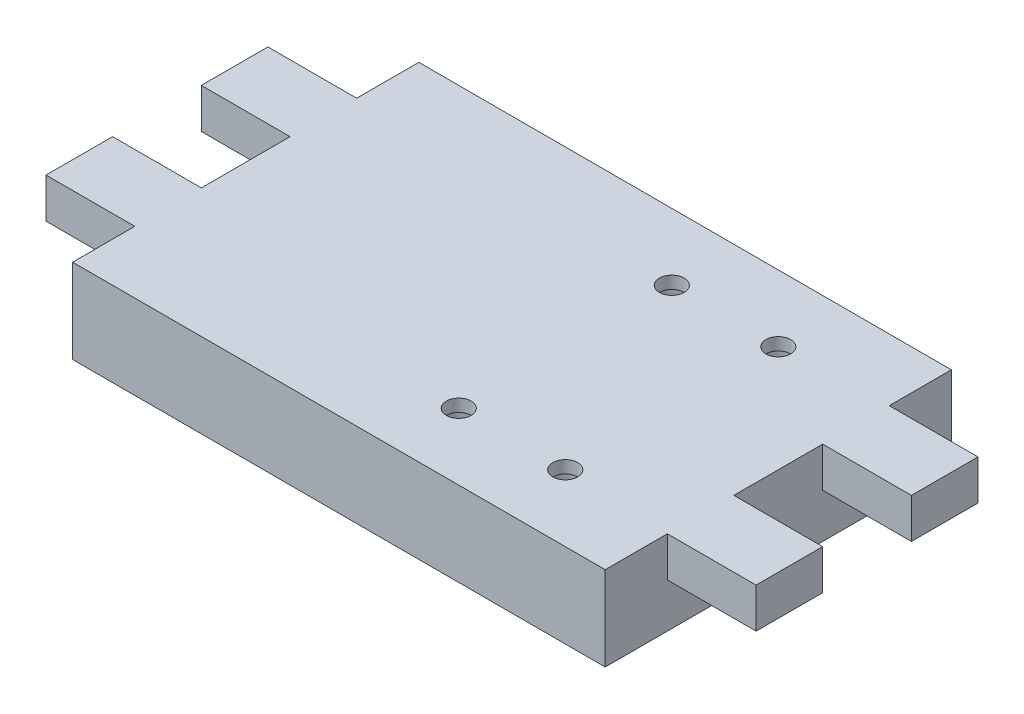
SolidWorks part; units mm, degrees
ref_plane "Front Plane" through (0, 0, 0) normal (0, 0, 1) x (1, 0, 0)
ref_plane "Top Plane" through (0, 0, 0) normal (0, 1, 0) x (1, 0, 0)
ref_plane "Right Plane" through (0, 0, 0) normal (1, 0, 0) x (0, 0, -1)
sketch "Sketch1" plane through (0, 0, 0) normal (1, 0, 0) x (0, 0, -1)
  line L1 (-12.5, -2.25) -> (12.5, -2.25)
  line L2 (-12.5, -2.25) -> (-12.5, 2.25)
  line L3 (-12.5, 2.25) -> (12.5, 2.25)
  line L4 (12.5, -2.25) -> (12.5, 2.25)
  line L5 (-12.5, -2.25) -> (12.5, 2.25) construction
  line L6 (-12.5, 2.25) -> (12.5, -2.25) construction
  point P0 (0, 0)
  dimension "D1" = 4.5
  dimension "D2" = 25
extrude "Boss-Extrude1" add sketch "Sketch1" along normal mid plane 60
sketch "Sketch2" plane through (30, 0, 0) normal (1, 0, 0) x (0, 0, -1)
  line L5 (12.5, 2.25) -> (-12.5, 2.25) construction
  line L6 (-12.5, 2.25) -> (-5, 2.25)
  line L7 (-12.5, 2.25) -> (-12.5, -2.25)
  line L8 (-12.5, -2.25) -> (-5, -2.25)
  line L9 (-5, 2.25) -> (-5, -2.25)
  line L10 (5, 2.25) -> (12.5, 2.25)
  line L11 (5, 2.25) -> (5, -2.25)
  line L12 (5, -2.25) -> (12.5, -2.25)
  line L13 (12.5, 2.25) -> (12.5, -2.25)
  line L14 (-12.5, -2.25) -> (12.5, -2.25) construction
  line L15 (-12.5, 2.25) -> (-12.5, -2.25) construction
  line L16 (12.5, -2.25) -> (12.5, 2.25) construction
  dimension "D1" = 7.5
  dimension "D2" = 7.5
extrude "Boss-Extrude2" add sketch "Sketch2" along normal blind 10
sketch "Esquisse1" plane through (0, 0, 12.5) normal (0, 0, 1) x (1, 0, 0)
  line L0 (40, -2.25) -> (-30, -2.25) construction
  line L1 (-30, 2.25) -> (30, 2.25)
  line L2 (-30, 2.25) -> (-30, -2.25)
  line L3 (-30, -2.25) -> (30, -2.25)
  line L4 (30, 2.25) -> (30, -2.25)
  dimension "D1" = 60
extrude "Boss.-Extru.1" add sketch "Esquisse1" along normal blind 7
mirror "Symétrie1" about plane through (0, 0, 0) normal (0, 0, 1) of "Boss.-Extru.1"
mirror "Mirror1" about plane through (0, 0, 0) normal (1, 0, 0) of "Boss-Extrude2"
sketch "Sketch6" plane through (0, -2.25, 0) normal (0, -1, 0) x (1, 0, 0)
  line L0 (-30, 19.5) -> (-30, -19.5)
  line L1 (-30, -19.5) -> (30, -19.5)
  line L2 (30, -19.5) -> (30, 19.5)
  line L3 (30, 19.5) -> (-30, 19.5)
extrude "Boss-Extrude3" add sketch "Sketch6" along normal blind 5
hole_wizard "CBORE for M3 SBHCS2" positions "Sketch4" profile "Sketch5" counterbore size "M3" standard "ANSI Metric" end condition through all
sketch "Sketch4" plane through (0, -7.25, 0) normal (0, -1, 0) x (-1, 0, 0)
  line L0 (-18, 12) -> (-18, -12) construction
  line L1 (-18, -12) -> (-6, -12) construction
  line L2 (-6, -12) -> (-6, 12) construction
  line L3 (-6, 12) -> (-18, 12) construction
  line L4 (-30, 19.5) -> (-30, -19.5) construction
  point P0 (-18, 12)
  point P3 (-6, 12)
  point P6 (-6, -12)
  point P9 (-18, -12)
  point P12 (-18, 12)
  point P13 (-18, -12)
  point P14 (-6, -12)
  point P15 (-6, 12)
  point P18 (-6, 0)
  point P21 (-14.8638, 12)
  dimension "D1" = 12
  dimension "D2" = 24
  dimension "D3" = 12
sketch "Sketch5" plane through (18, -7.25, -12) normal (1, 0, 0) x (0, 0, -1)
  line L0 (0, 0) -> (0, 9.5)
  line L1 (0, 9.5) -> (1.4, 9.5)
  line L3 (1.4, 9.5) -> (1.4, 8.1)
  line L4 (1.4, 8.1) -> (2.75, 8.1)
  line L5 (2.75, 8.1) -> (2.75, 0)
  line L7 (2.75, 0) -> (0, 0)
  line L11 (0, -6.35) -> (0, 107.95) construction
  dimension "Thru Hole Dia." = 2.8
  dimension "Thru Hole Depth" = 9.5
  dimension "C'Bore Dia." = 5.5
  dimension "C'Bore Depth" = 8.1
